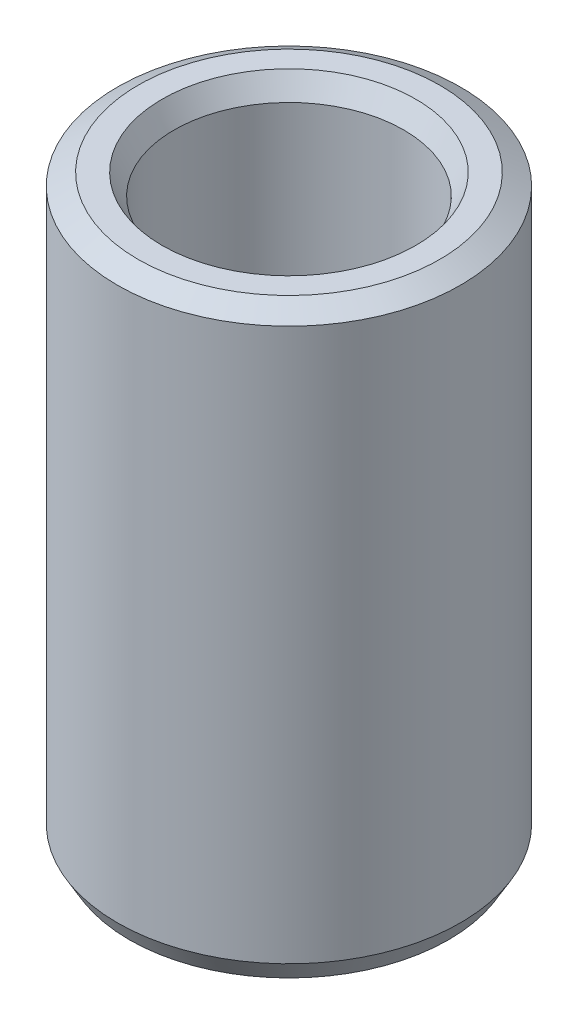
SolidWorks part; units mm, degrees
ref_plane "Front Plane" through (0, 0, 0) normal (0, 0, 1) x (1, 0, 0)
ref_plane "Top Plane" through (0, 0, 0) normal (0, 1, 0) x (1, 0, 0)
ref_plane "Right Plane" through (0, 0, 0) normal (1, 0, 0) x (0, 0, -1)
sketch "Sketch1" plane through (0, 0, 0) normal (0, 1, 0) x (1, 0, 0)
  circle A0 centre (0, 0) radius 37.5
  dimension "SLEEVE_OD" = 75
extrude "Boss-Extrude1" add sketch "Sketch1" along normal blind 127.8079
sketch "Sketch2" plane through (0, 0, 0) normal (0, 1, 0) x (1, 0, 0)
  circle A0 centre (0, 0) radius 25.0955
  dimension "BORE_D" = 50.1911
extrude "Cut-Extrude1" cut sketch "Sketch2" along normal through all
chamfer "Chamfer1" distance 2.6141 angle 60 4 edges at (0, 127.8079, 25.0955) (0, 0, 25.0955) (0, 0, 37.5) (0, 127.8079, 37.5) first distance on face at (0, 127.8079, 25.0955) first distance on face at (0, 0, 25.0955) first distance on face at (0, 127.8079, 37.5)
